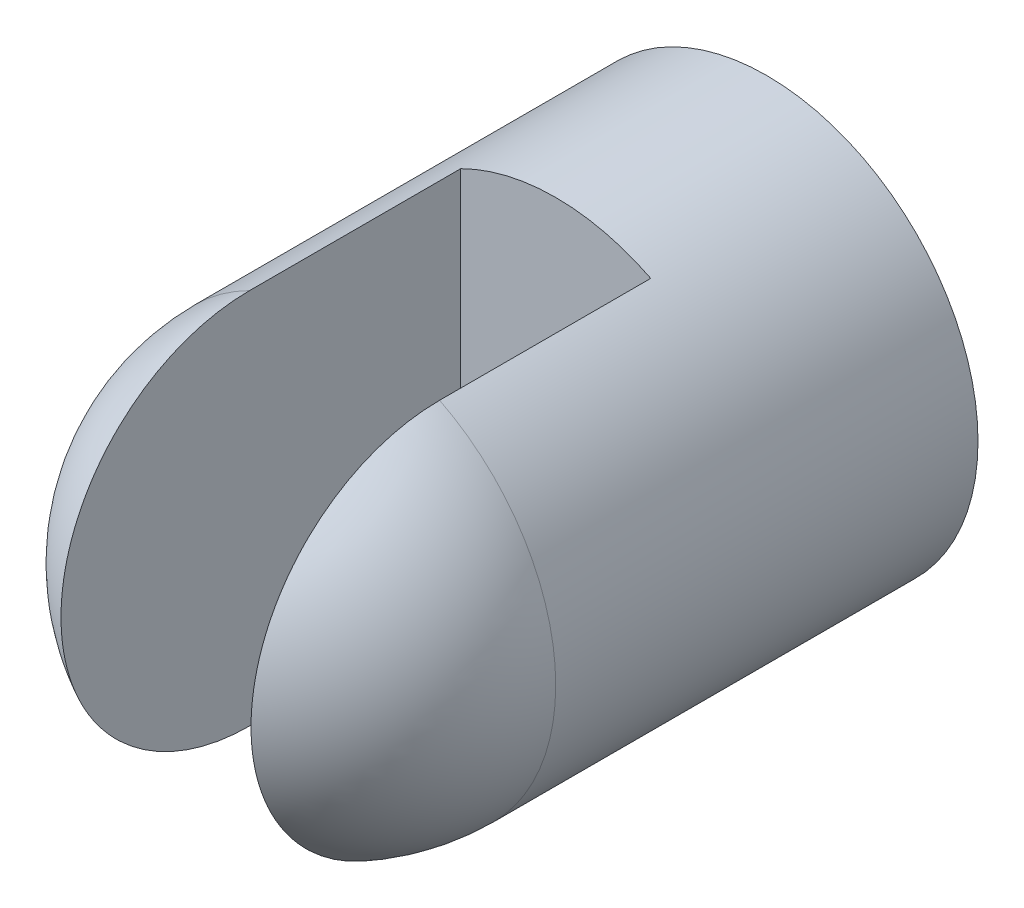
SolidWorks part; units mm, degrees
ref_plane "Front Plane" through (0, 0, 0) normal (0, 0, 1) x (1, 0, 0)
ref_plane "Top Plane" through (0, 0, 0) normal (0, 1, 0) x (1, 0, 0)
ref_plane "Right Plane" through (0, 0, 0) normal (1, 0, 0) x (0, 0, -1)
sketch "Sketch1" plane through (0, 0, 0) normal (0, 0, 1) x (1, 0, 0)
  circle A0 centre (0, 0) radius 100
  dimension "D1" = 200
extrude "Boss-Extrude2" add sketch "Sketch1" along normal blind 200
dome "Dome1" faces to dome 1 distance 100 reverse direction no elliptical dome no face at (100, 0, 200) parameters "D1"=100
ref_plane "Plane1" through (0, 0, 300) normal (0, 0, 1) x (1, 0, 0)
sketch "Sketch3" plane through (0, 0, 300) normal (0, 0, 1) x (1, 0, 0)
  line L1 (45, -110.5405) -> (-45, -110.5405)
  line L2 (45, -110.5405) -> (45, 110.5405)
  line L3 (45, 110.5405) -> (-45, 110.5405)
  line L4 (-45, -110.5405) -> (-45, 110.5405)
  line L5 (45, -110.5405) -> (-45, 110.5405) construction
  line L6 (45, 110.5405) -> (-45, -110.5405) construction
  point P0 (0, 0)
  dimension "D1" = 90
extrude "Cut-Extrude1" cut sketch "Sketch3" against normal blind 200
sketch "Sketch4" plane through (0, 0, 0) normal (0, 0, -1) x (-1, 0, 0)
  circle A0 centre (0, 0) radius 40
  dimension "D1" = 80
extrude "Boss-Extrude3" add sketch "Sketch4" along normal blind 5
